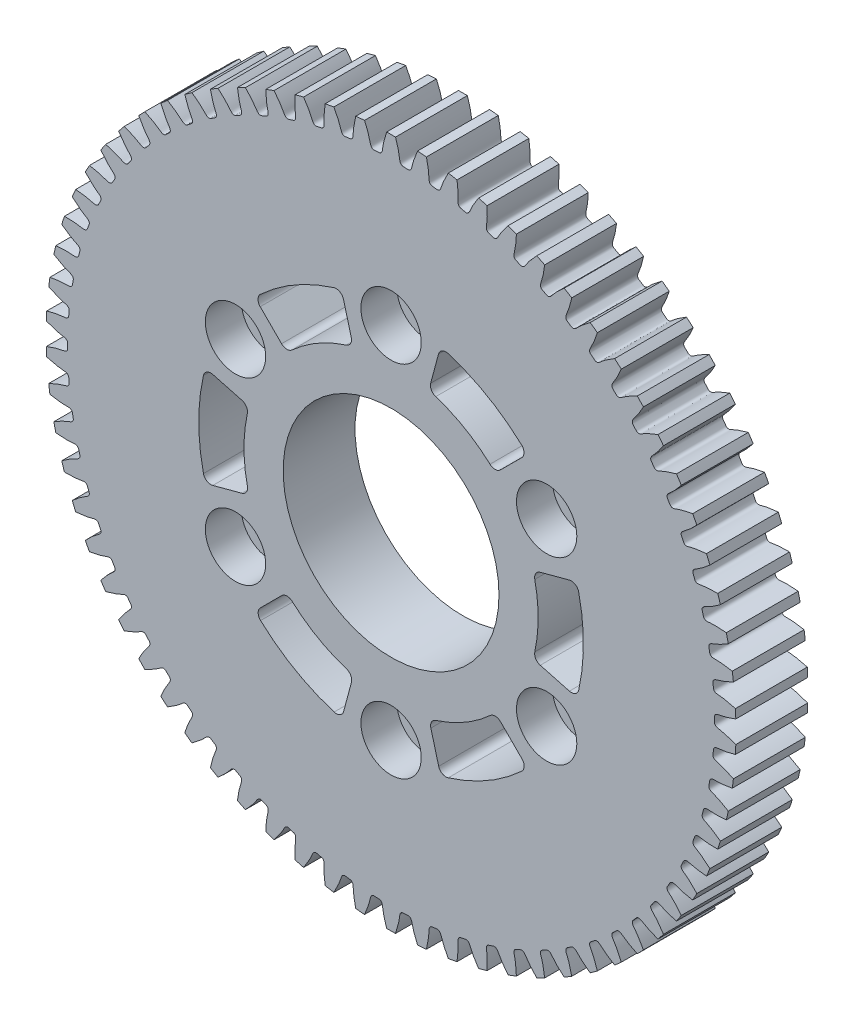
SolidWorks part; units mm, degrees
material "7075-T6 (SN)"
ref_plane "Front Plane" through (0, 0, 0) normal (0, 0, 1) x (1, 0, 0)
ref_plane "Top Plane" through (0, 0, 0) normal (0, 1, 0) x (1, 0, 0)
ref_plane "Right Plane" through (0, 0, 0) normal (1, 0, 0) x (0, 0, -1)
ref_plane "Plane1" through (0, 0, 4.7625) normal (0, 0, 1) x (1, 0, 0)
sketch "Sketch1" plane through (0, 0, 4.7625) normal (0, 0, 1) x (1, 0, 0)
  arc A0 (45.6439, -2.6368) -> (45.6965, -1.4653) centre (0, 0) ccw
  arc A1 (45.6965, 1.4653) -> (45.6439, 2.6368) centre (0, 0) ccw
  arc A2 (45.3812, 5.5556) -> (45.2238, 6.7177) centre (0, 0) ccw
  arc A3 (44.7005, 9.6011) -> (44.4396, 10.7445) centre (0, 0) ccw
  arc A4 (43.6599, 13.5694) -> (43.2975, 14.6848) centre (0, 0) ccw
  arc A5 (42.2678, 17.4284) -> (41.8069, 18.5068) centre (0, 0) ccw
  arc A6 (40.5354, 21.1471) -> (39.9797, 22.1799) centre (0, 0) ccw
  arc A7 (38.4766, 24.6956) -> (37.8305, 25.6743) centre (0, 0) ccw
  arc A8 (36.108, 28.0452) -> (35.3768, 28.9621) centre (0, 0) ccw
  arc A9 (33.4487, 31.169) -> (32.6382, 32.0166) centre (0, 0) ccw
  arc A10 (30.5201, 34.0418) -> (29.6369, 34.8134) centre (0, 0) ccw
  arc A11 (27.3457, 36.6406) -> (26.3969, 37.3299) centre (0, 0) ccw
  arc A12 (23.9512, 38.9443) -> (22.9445, 39.5458) centre (0, 0) ccw
  arc A13 (20.3638, 40.9345) -> (19.3072, 41.4433) centre (0, 0) ccw
  arc A14 (16.6125, 42.5951) -> (15.5145, 43.0072) centre (0, 0) ccw
  arc A15 (12.7274, 43.9128) -> (11.597, 44.2248) centre (0, 0) ccw
  arc A16 (8.7399, 44.8769) -> (7.586, 45.0863) centre (0, 0) ccw
  arc A17 (4.682, 45.4796) -> (3.514, 45.5848) centre (0, 0) ccw
  arc A18 (0.5864, 45.7162) -> (-0.5864, 45.7162) centre (0, 0) ccw
  arc A19 (-3.514, 45.5848) -> (-4.682, 45.4796) centre (0, 0) ccw
  arc A20 (-7.586, 45.0863) -> (-8.7399, 44.8769) centre (0, 0) ccw
  arc A21 (-11.597, 44.2248) -> (-12.7274, 43.9128) centre (0, 0) ccw
  arc A22 (-15.5145, 43.0072) -> (-16.6125, 42.5951) centre (0, 0) ccw
  arc A23 (-19.3072, 41.4433) -> (-20.3638, 40.9345) centre (0, 0) ccw
  arc A24 (-22.9445, 39.5458) -> (-23.9512, 38.9443) centre (0, 0) ccw
  arc A25 (-26.3969, 37.3299) -> (-27.3457, 36.6406) centre (0, 0) ccw
  arc A26 (-29.6369, 34.8134) -> (-30.5201, 34.0418) centre (0, 0) ccw
  arc A27 (-32.6382, 32.0166) -> (-33.4487, 31.169) centre (0, 0) ccw
  arc A28 (-35.3768, 28.9621) -> (-36.108, 28.0452) centre (0, 0) ccw
  arc A29 (-37.8305, 25.6743) -> (-38.4766, 24.6956) centre (0, 0) ccw
  arc A30 (-39.9797, 22.1799) -> (-40.5354, 21.1471) centre (0, 0) ccw
  arc A31 (-41.8069, 18.5068) -> (-42.2678, 17.4284) centre (0, 0) ccw
  arc A32 (-43.2975, 14.6848) -> (-43.6599, 13.5694) centre (0, 0) ccw
  arc A33 (-44.4396, 10.7445) -> (-44.7005, 9.6011) centre (0, 0) ccw
  arc A34 (-45.2238, 6.7177) -> (-45.3812, 5.5556) centre (0, 0) ccw
  arc A35 (-45.6439, 2.6368) -> (-45.6965, 1.4653) centre (0, 0) ccw
  arc A36 (-45.6965, -1.4653) -> (-45.6439, -2.6368) centre (0, 0) ccw
  arc A37 (-45.3812, -5.5556) -> (-45.2238, -6.7177) centre (0, 0) ccw
  arc A38 (-44.7005, -9.6011) -> (-44.4396, -10.7445) centre (0, 0) ccw
  arc A39 (-43.6599, -13.5694) -> (-43.2975, -14.6848) centre (0, 0) ccw
  arc A40 (-42.2678, -17.4284) -> (-41.8069, -18.5068) centre (0, 0) ccw
  arc A41 (-40.5354, -21.1471) -> (-39.9797, -22.1799) centre (0, 0) ccw
  arc A42 (-38.4766, -24.6956) -> (-37.8305, -25.6743) centre (0, 0) ccw
  arc A43 (-36.108, -28.0452) -> (-35.3768, -28.9621) centre (0, 0) ccw
  arc A44 (-33.4487, -31.169) -> (-32.6382, -32.0166) centre (0, 0) ccw
  arc A45 (-30.5201, -34.0418) -> (-29.6369, -34.8134) centre (0, 0) ccw
  arc A46 (-27.3457, -36.6406) -> (-26.3969, -37.3299) centre (0, 0) ccw
  arc A47 (-23.9512, -38.9443) -> (-22.9445, -39.5458) centre (0, 0) ccw
  arc A48 (-20.3638, -40.9345) -> (-19.3072, -41.4433) centre (0, 0) ccw
  arc A49 (-16.6125, -42.5951) -> (-15.5145, -43.0072) centre (0, 0) ccw
  arc A50 (-12.7274, -43.9128) -> (-11.597, -44.2248) centre (0, 0) ccw
  arc A51 (-8.7399, -44.8769) -> (-7.586, -45.0863) centre (0, 0) ccw
  arc A52 (-4.682, -45.4796) -> (-3.514, -45.5848) centre (0, 0) ccw
  arc A53 (-0.5864, -45.7162) -> (0.5864, -45.7162) centre (0, 0) ccw
  arc A54 (3.514, -45.5848) -> (4.682, -45.4796) centre (0, 0) ccw
  arc A55 (7.586, -45.0863) -> (8.7399, -44.8769) centre (0, 0) ccw
  arc A56 (11.597, -44.2248) -> (12.7274, -43.9128) centre (0, 0) ccw
  arc A57 (15.5145, -43.0072) -> (16.6125, -42.5951) centre (0, 0) ccw
  arc A58 (19.3072, -41.4433) -> (20.3638, -40.9345) centre (0, 0) ccw
  arc A59 (22.9445, -39.5458) -> (23.9512, -38.9443) centre (0, 0) ccw
  arc A60 (26.3969, -37.3299) -> (27.3457, -36.6406) centre (0, 0) ccw
  arc A61 (29.6369, -34.8134) -> (30.5201, -34.0418) centre (0, 0) ccw
  arc A62 (32.6382, -32.0166) -> (33.4487, -31.169) centre (0, 0) ccw
  arc A63 (35.3768, -28.9621) -> (36.108, -28.0452) centre (0, 0) ccw
  arc A64 (37.8305, -25.6743) -> (38.4766, -24.6956) centre (0, 0) ccw
  arc A65 (39.9797, -22.1799) -> (40.5354, -21.1471) centre (0, 0) ccw
  arc A66 (41.8069, -18.5068) -> (42.2678, -17.4284) centre (0, 0) ccw
  arc A67 (43.2975, -14.6848) -> (43.6599, -13.5694) centre (0, 0) ccw
  arc A68 (44.4396, -10.7445) -> (44.7005, -9.6011) centre (0, 0) ccw
  arc A69 (45.2238, -6.7177) -> (45.3812, -5.5556) centre (0, 0) ccw
  spline S0 degree 3 number of poles 75 (45.3812, -5.5556) -> (45.6439, -2.6368)
  spline S1 degree 3 number of poles 75 (45.6965, -1.4653) -> (45.6965, 1.4653)
  spline S2 degree 3 number of poles 75 (45.6439, 2.6368) -> (45.3812, 5.5556)
  spline S3 degree 3 number of poles 75 (45.2238, 6.7177) -> (44.7005, 9.6011)
  spline S4 degree 3 number of poles 75 (44.4396, 10.7445) -> (43.6599, 13.5694)
  spline S5 degree 3 number of poles 75 (43.2975, 14.6848) -> (42.2678, 17.4284)
  spline S6 degree 3 number of poles 75 (41.8069, 18.5068) -> (40.5354, 21.1471)
  spline S7 degree 3 number of poles 75 (39.9797, 22.1799) -> (38.4766, 24.6956)
  spline S8 degree 3 number of poles 75 (37.8305, 25.6743) -> (36.108, 28.0452)
  spline S9 degree 3 number of poles 75 (35.3768, 28.9621) -> (33.4487, 31.169)
  spline S10 degree 3 number of poles 75 (32.6382, 32.0166) -> (30.5201, 34.0418)
  spline S11 degree 3 number of poles 75 (29.6369, 34.8134) -> (27.3457, 36.6406)
  spline S12 degree 3 number of poles 75 (26.3969, 37.3299) -> (23.9512, 38.9443)
  spline S13 degree 3 number of poles 75 (22.9445, 39.5458) -> (20.3638, 40.9345)
  spline S14 degree 3 number of poles 75 (19.3072, 41.4433) -> (16.6125, 42.5951)
  spline S15 degree 3 number of poles 75 (15.5145, 43.0072) -> (12.7274, 43.9128)
  spline S16 degree 3 number of poles 75 (11.597, 44.2248) -> (8.7399, 44.8769)
  spline S17 degree 3 number of poles 75 (7.586, 45.0863) -> (4.682, 45.4796)
  spline S18 degree 3 number of poles 75 (3.514, 45.5848) -> (0.5864, 45.7162)
  spline S19 degree 3 number of poles 75 (-0.5864, 45.7162) -> (-3.514, 45.5848)
  spline S20 degree 3 number of poles 75 (-4.682, 45.4796) -> (-7.586, 45.0863)
  spline S21 degree 3 number of poles 75 (-8.7399, 44.8769) -> (-11.597, 44.2248)
  spline S22 degree 3 number of poles 75 (-12.7274, 43.9128) -> (-15.5145, 43.0072)
  spline S23 degree 3 number of poles 75 (-16.6125, 42.5951) -> (-19.3072, 41.4433)
  spline S24 degree 3 number of poles 75 (-20.3638, 40.9345) -> (-22.9445, 39.5458)
  spline S25 degree 3 number of poles 75 (-23.9512, 38.9443) -> (-26.3969, 37.3299)
  spline S26 degree 3 number of poles 75 (-27.3457, 36.6406) -> (-29.6369, 34.8134)
  spline S27 degree 3 number of poles 75 (-30.5201, 34.0418) -> (-32.6382, 32.0166)
  spline S28 degree 3 number of poles 75 (-33.4487, 31.169) -> (-35.3768, 28.9621)
  spline S29 degree 3 number of poles 75 (-36.108, 28.0452) -> (-37.8305, 25.6743)
  spline S30 degree 3 number of poles 75 (-38.4766, 24.6956) -> (-39.9797, 22.1799)
  spline S31 degree 3 number of poles 75 (-40.5354, 21.1471) -> (-41.8069, 18.5068)
  spline S32 degree 3 number of poles 75 (-42.2678, 17.4284) -> (-43.2975, 14.6848)
  spline S33 degree 3 number of poles 75 (-43.6599, 13.5694) -> (-44.4396, 10.7445)
  spline S34 degree 3 number of poles 75 (-44.7005, 9.6011) -> (-45.2238, 6.7177)
  spline S35 degree 3 number of poles 75 (-45.3812, 5.5556) -> (-45.6439, 2.6368)
  spline S36 degree 3 number of poles 75 (-45.6965, 1.4653) -> (-45.6965, -1.4653)
  spline S37 degree 3 number of poles 75 (-45.6439, -2.6368) -> (-45.3812, -5.5556)
  spline S38 degree 3 number of poles 75 (-45.2238, -6.7177) -> (-44.7005, -9.6011)
  spline S39 degree 3 number of poles 75 (-44.4396, -10.7445) -> (-43.6599, -13.5694)
  spline S40 degree 3 number of poles 75 (-43.2975, -14.6848) -> (-42.2678, -17.4284)
  spline S41 degree 3 number of poles 75 (-41.8069, -18.5068) -> (-40.5354, -21.1471)
  spline S42 degree 3 number of poles 75 (-39.9797, -22.1799) -> (-38.4766, -24.6956)
  spline S43 degree 3 number of poles 75 (-37.8305, -25.6743) -> (-36.108, -28.0452)
  spline S44 degree 3 number of poles 75 (-35.3768, -28.9621) -> (-33.4487, -31.169)
  spline S45 degree 3 number of poles 75 (-32.6382, -32.0166) -> (-30.5201, -34.0418)
  spline S46 degree 3 number of poles 75 (-29.6369, -34.8134) -> (-27.3457, -36.6406)
  spline S47 degree 3 number of poles 75 (-26.3969, -37.3299) -> (-23.9512, -38.9443)
  spline S48 degree 3 number of poles 75 (-22.9445, -39.5458) -> (-20.3638, -40.9345)
  spline S49 degree 3 number of poles 75 (-19.3072, -41.4433) -> (-16.6125, -42.5951)
  spline S50 degree 3 number of poles 75 (-15.5145, -43.0072) -> (-12.7274, -43.9128)
  spline S51 degree 3 number of poles 75 (-11.597, -44.2248) -> (-8.7399, -44.8769)
  spline S52 degree 3 number of poles 75 (-7.586, -45.0863) -> (-4.682, -45.4796)
  spline S53 degree 3 number of poles 75 (-3.514, -45.5848) -> (-0.5864, -45.7162)
  spline S54 degree 3 number of poles 75 (0.5864, -45.7162) -> (3.514, -45.5848)
  spline S55 degree 3 number of poles 75 (4.682, -45.4796) -> (7.586, -45.0863)
  spline S56 degree 3 number of poles 75 (8.7399, -44.8769) -> (11.597, -44.2248)
  spline S57 degree 3 number of poles 75 (12.7274, -43.9128) -> (15.5145, -43.0072)
  spline S58 degree 3 number of poles 75 (16.6125, -42.5951) -> (19.3072, -41.4433)
  spline S59 degree 3 number of poles 75 (20.3638, -40.9345) -> (22.9445, -39.5458)
  spline S60 degree 3 number of poles 75 (23.9512, -38.9443) -> (26.3969, -37.3299)
  spline S61 degree 3 number of poles 75 (27.3457, -36.6406) -> (29.6369, -34.8134)
  spline S62 degree 3 number of poles 75 (30.5201, -34.0418) -> (32.6382, -32.0166)
  spline S63 degree 3 number of poles 75 (33.4487, -31.169) -> (35.3768, -28.9621)
  spline S64 degree 3 number of poles 75 (36.108, -28.0452) -> (37.8305, -25.6743)
  spline S65 degree 3 number of poles 75 (38.4766, -24.6956) -> (39.9797, -22.1799)
  spline S66 degree 3 number of poles 75 (40.5354, -21.1471) -> (41.8069, -18.5068)
  spline S67 degree 3 number of poles 75 (42.2678, -17.4284) -> (43.2975, -14.6848)
  spline S68 degree 3 number of poles 75 (43.6599, -13.5694) -> (44.4396, -10.7445)
  spline S69 degree 3 number of poles 75 (44.7005, -9.6011) -> (45.2238, -6.7177)
extrude "Boss-Extrude1" add sketch "Sketch1" against normal blind 9.525
sketch "Sketch2" plane through (0, 0, 4.7625) normal (0, 0, 1) x (1, 0, 0)
  line L0 (-18.0671, 17.9953) -> (-13.8245, 13.7526)
  line L1 (-5.0224, 18.8421) -> (-6.5753, 24.6377)
  arc A0 (-6.5753, 24.6377) -> (-18.0671, 17.9953) centre (0, 0) ccw
  arc A1 (-13.8245, 13.7526) -> (-5.0224, 18.8421) centre (0, 0) cw
extrude "Cut-Extrude1" cut sketch "Sketch2" against normal through all
sketch "Sketch3" plane through (0, 0, 4.7625) normal (0, 0, 1) x (1, 0, 0)
  line L0 (13.8065, 13.7706) -> (18.0492, 18.0133)
  line L1 (6.5508, 24.6442) -> (4.9979, 18.8486)
  arc A0 (18.0492, 18.0133) -> (6.5508, 24.6442) centre (0, 0) ccw
  arc A1 (4.9979, 18.8486) -> (13.8065, 13.7706) centre (0, 0) cw
extrude "Cut-Extrude2" cut sketch "Sketch3" against normal through all
sketch "Sketch4" plane through (0, 0, 4.7625) normal (0, 0, 1) x (1, 0, 0)
  line L0 (18.829, -5.0715) -> (24.6245, -6.6244)
  line L1 (24.6179, 6.6489) -> (18.8223, 5.096)
  arc A0 (24.6245, -6.6244) -> (24.6179, 6.6489) centre (0, 0) ccw
  arc A1 (18.8223, 5.096) -> (18.829, -5.0715) centre (0, 0) cw
extrude "Cut-Extrude3" cut sketch "Sketch4" against normal through all
sketch "Sketch5" plane through (0, 0, 4.7625) normal (0, 0, 1) x (1, 0, 0)
  line L0 (18.0671, -17.9953) -> (13.8245, -13.7526)
  line L1 (5.0224, -18.8421) -> (6.5753, -24.6377)
  arc A0 (6.5753, -24.6377) -> (18.0671, -17.9953) centre (0, 0) ccw
  arc A1 (13.8245, -13.7526) -> (5.0224, -18.8421) centre (0, 0) cw
extrude "Cut-Extrude4" cut sketch "Sketch5" against normal through all
sketch "Sketch6" plane through (0, 0, 4.7625) normal (0, 0, 1) x (1, 0, 0)
  line L0 (-6.5508, -24.6442) -> (-4.9979, -18.8486)
  line L1 (-13.8065, -13.7706) -> (-18.0492, -18.0133)
  arc A0 (-18.0492, -18.0133) -> (-6.5508, -24.6442) centre (0, 0) ccw
  arc A1 (-4.9979, -18.8486) -> (-13.8065, -13.7706) centre (0, 0) cw
extrude "Cut-Extrude5" cut sketch "Sketch6" against normal through all
sketch "Sketch7" plane through (0, 0, -4.7625) normal (0, 0, -1) x (-1, 0, 0)
  line L0 (24.6245, 6.6244) -> (18.829, 5.0715)
  line L1 (18.8223, -5.096) -> (24.6179, -6.6489)
  arc A0 (24.6179, -6.6489) -> (24.6245, 6.6244) centre (0, 0) ccw
  arc A1 (18.829, 5.0715) -> (18.8223, -5.096) centre (0, 0) cw
extrude "Cut-Extrude6" cut sketch "Sketch7" against normal through all
hole_wizard "M25 Clearance Hole1" positions "Sketch9" profile "Sketch8" hole size "M25" standard "ANSI Metric"
sketch "Sketch9" plane through (0, 0, 4.7625) normal (0, 0, 1) x (1, 0, 0)
  point P0 (0, 0)
sketch "Sketch8" plane through (0, 0, 4.7625) normal (1, 0, 0) x (0, -1, 0)
  line L0 (0, 0) -> (0, 9.525)
  line L1 (0, 9.525) -> (14.3065, 9.525)
  line L2 (14.3065, 9.525) -> (14.3065, 0)
  line L5 (14.3065, 0) -> (0, 0)
  line L11 (0, -6.35) -> (0, 107.95) construction
  dimension "Thru Hole Dia." = 28.6131
  dimension "Thru Hole Depth" = 9.525
hole_wizard "CBORE for M4 Hex Head Machine Screw1" positions "Sketch11" profile "Sketch10" counterbore size "M4" standard "ANSI Metric"
sketch "Sketch11" plane through (0, 0, 4.7625) normal (0, 0, 1) x (1, 0, 0)
  point P0 (20.6222, -11.9063)
  point P1 (-20.6222, -11.9062)
  point P2 (0, 23.8125)
  point P3 (-20.6222, 11.9063)
  point P4 (0, -23.8125)
  point P5 (20.6222, 11.9062)
sketch "Sketch10" plane through (20.6222, -11.9063, 4.7625) normal (1, 0, 0) x (0, -1, 0)
  line L0 (0, 0) -> (0, 9.525)
  line L1 (0, 9.525) -> (2.15, 9.525)
  line L3 (2.15, 9.525) -> (2.15, 4.7625)
  line L4 (2.15, 4.7625) -> (4, 4.7625)
  line L5 (4, 4.7625) -> (4, 0)
  line L7 (4, 0) -> (0, 0)
  line L11 (0, -6.35) -> (0, 107.95) construction
  dimension "Thru Hole Dia." = 4.3
  dimension "Thru Hole Depth" = 9.525
  dimension "C'Bore Dia." = 8
  dimension "C'Bore Depth" = 4.7625
fillet "Fillet1" radius 1 24 edges at (18.8223, 5.096, 0) (-13.8245, 13.7526, 0) (4.9979, 18.8486, 0) (-18.829, 5.0715, 0) (18.829, -5.0715, 0) (-24.6179, -6.6489, 0) (13.8065, 13.7706, 0) (-18.8223, -5.096, 0) (-5.0224, 18.8421, 0) (-18.0492, -18.0133, 0) (24.6245, -6.6244, 0) (-13.8065, -13.7706, 0) (24.6179, 6.6489, 0) (-6.5508, -24.6442, 0) (18.0492, 18.0133, 0) (-4.9979, -18.8486, 0) (6.5508, 24.6442, 0) (6.5753, -24.6377, 0) (-6.5753, 24.6377, 0) (5.0224, -18.8421, 0) (-18.0671, 17.9953, 0) (18.0671, -17.9953, 0) (-24.6245, 6.6244, 0) (13.8245, -13.7526, 0) tangent propagation no
